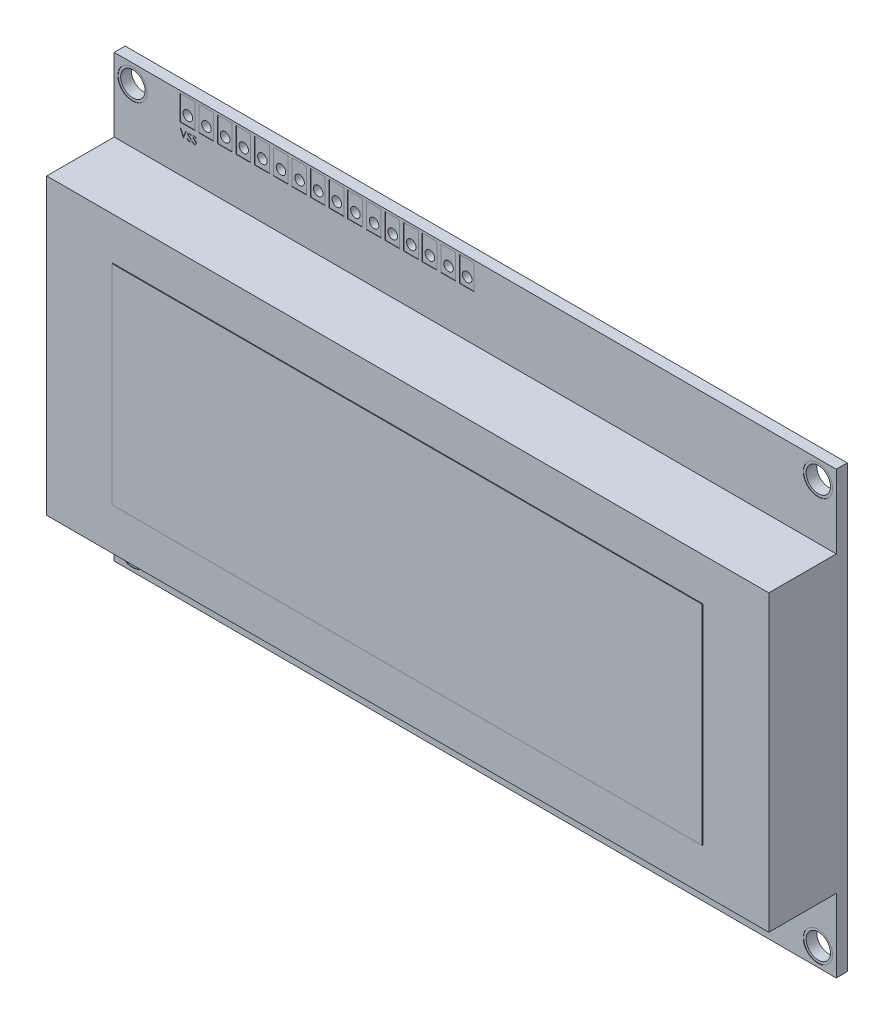
SolidWorks part; units mm, degrees
ref_plane "Front Plane" through (0, 0, 0) normal (0, 0, 1) x (1, 0, 0)
ref_plane "Top Plane" through (0, 0, 0) normal (0, 1, 0) x (1, 0, 0)
ref_plane "Right Plane" through (0, 0, 0) normal (1, 0, 0) x (0, 0, -1)
sketch "Sketch1" plane through (0, 0, 0) normal (0, 0, 1) x (1, 0, 0)
  line L0 (0, 40.8512) -> (0, -48.0365) construction
  line L1 (49.25, -30.05) -> (-49.25, -30.05)
  line L2 (49.25, -30.05) -> (49.25, 30.05)
  line L3 (49.25, 30.05) -> (-49.25, 30.05)
  line L4 (-49.25, -30.05) -> (-49.25, 30.05)
  line L5 (49.25, -30.05) -> (-49.25, 30.05) construction
  line L6 (49.25, 30.05) -> (-49.25, -30.05) construction
  line L7 (-58.2061, 0) -> (68.8537, 0) construction
  circle A0 centre (-46.75, 27.55) radius 1.665
  circle A1 centre (46.75, 27.55) radius 1.665
  circle A2 centre (-46.75, -27.55) radius 1.665
  circle A3 centre (46.75, -27.55) radius 1.665
  circle A4 centre (-39.25, 27.55) radius 0.65
  circle A5 centre (-36.71, 27.55) radius 0.65
  circle A6 centre (-34.17, 27.55) radius 0.65
  circle A7 centre (-31.63, 27.55) radius 0.65
  circle A8 centre (-29.09, 27.55) radius 0.65
  circle A9 centre (-26.55, 27.55) radius 0.65
  circle A10 centre (-24.01, 27.55) radius 0.65
  circle A11 centre (-21.47, 27.55) radius 0.65
  circle A12 centre (-18.93, 27.55) radius 0.65
  circle A13 centre (-16.39, 27.55) radius 0.65
  circle A14 centre (-13.85, 27.55) radius 0.65
  circle A15 centre (-11.31, 27.55) radius 0.65
  circle A16 centre (-8.77, 27.55) radius 0.65
  circle A17 centre (-6.23, 27.55) radius 0.65
  circle A18 centre (-3.69, 27.55) radius 0.65
  circle A19 centre (-1.15, 27.55) radius 0.65
  point P0 (0, 0)
  dimension "D5" = 3.33
  dimension "D6" = 1.3
  dimension "D1" = 98.5
  dimension "D2" = 60.1
  dimension "D3" = 2.5
  dimension "D4" = 2.5
  dimension "D7" = 2.5
  dimension "D8" = 10
  dimension "D10" = 2.54
  dimension "D9" = 16
extrude "Boss-Extrude1" add sketch "Sketch1" along normal mid plane 1.5
sketch "Sketch2" plane through (0, 0, 0.75) normal (0, 0, 1) x (1, 0, 0)
  line L0 (-49.25, 30.05) -> (-49.25, -30.05) construction
  line L1 (49.25, -20.05) -> (-49.25, -20.05)
  line L2 (49.25, -20.05) -> (49.25, 20.05)
  line L3 (49.25, 20.05) -> (-49.25, 20.05)
  line L4 (-49.25, -20.05) -> (-49.25, 20.05)
  line L5 (49.25, -20.05) -> (-49.25, 20.05) construction
  line L6 (49.25, 20.05) -> (-49.25, -20.05) construction
  line L7 (49.25, 30.05) -> (-49.25, 30.05) construction
  point P0 (0, 0)
  dimension "D1" = 10
  dimension "D2" = 40.1
  dimension "D3" = 98.5
extrude "Boss-Extrude2" add sketch "Sketch2" along normal blind 9.2
sketch "Sketch3" plane through (0, 0, 9.95) normal (0, 0, 1) x (1, 0, 0)
  line L0 (-49.25, 20.05) -> (-49.25, -20.05) construction
  line L1 (40.25, -14.25) -> (-40.25, -14.25)
  line L2 (40.25, -14.25) -> (40.25, 14.25)
  line L3 (40.25, 14.25) -> (-40.25, 14.25)
  line L4 (-40.25, -14.25) -> (-40.25, 14.25)
  line L5 (40.25, -14.25) -> (-40.25, 14.25) construction
  line L6 (40.25, 14.25) -> (-40.25, -14.25) construction
  line L7 (49.25, 20.05) -> (-49.25, 20.05) construction
  point P0 (0, 0)
  dimension "D1" = 9
  dimension "D2" = 5.8
extrude "Boss-Extrude3" add sketch "Sketch3" along normal blind 0.1
sketch "Sketch4" plane through (0, 0, 0.75) normal (0, 0, 1) x (1, 0, 0)
  line L0 (0, 45.5389) -> (0, -39.1221) construction
  line L1 (-62.9284, 0) -> (59.0171, 0) construction
  line L2 (-37.71, 29.7169) -> (-37.71, 26.3169)
  line L3 (-40.25, 29.7169) -> (-38.25, 29.7169)
  line L4 (-40.25, 29.7169) -> (-40.25, 26.3169)
  line L5 (-40.25, 26.3169) -> (-38.25, 26.3169)
  line L6 (-38.25, 29.7169) -> (-38.25, 26.3169)
  line L7 (-40.25, 29.7169) -> (-38.25, 26.3169) construction
  line L8 (-40.25, 26.3169) -> (-38.25, 29.7169) construction
  line L9 (-37.71, 29.7169) -> (-35.71, 29.7169)
  line L10 (-35.71, 29.7169) -> (-35.71, 26.3169)
  line L11 (-37.71, 26.3169) -> (-35.71, 26.3169)
  line L12 (-35.17, 29.7169) -> (-35.17, 26.3169)
  line L13 (-35.17, 29.7169) -> (-33.17, 29.7169)
  line L14 (-33.17, 29.7169) -> (-33.17, 26.3169)
  line L15 (-35.17, 26.3169) -> (-33.17, 26.3169)
  line L16 (-32.63, 29.7169) -> (-32.63, 26.3169)
  line L17 (-32.63, 29.7169) -> (-30.63, 29.7169)
  line L18 (-30.63, 29.7169) -> (-30.63, 26.3169)
  line L19 (-32.63, 26.3169) -> (-30.63, 26.3169)
  line L20 (-30.09, 29.7169) -> (-30.09, 26.3169)
  line L21 (-30.09, 29.7169) -> (-28.09, 29.7169)
  line L22 (-28.09, 29.7169) -> (-28.09, 26.3169)
  line L23 (-30.09, 26.3169) -> (-28.09, 26.3169)
  line L24 (-27.55, 29.7169) -> (-27.55, 26.3169)
  line L25 (-27.55, 29.7169) -> (-25.55, 29.7169)
  line L26 (-25.55, 29.7169) -> (-25.55, 26.3169)
  line L27 (-27.55, 26.3169) -> (-25.55, 26.3169)
  line L28 (-25.01, 29.7169) -> (-25.01, 26.3169)
  line L29 (-25.01, 29.7169) -> (-23.01, 29.7169)
  line L30 (-23.01, 29.7169) -> (-23.01, 26.3169)
  line L31 (-25.01, 26.3169) -> (-23.01, 26.3169)
  line L32 (-22.47, 29.7169) -> (-22.47, 26.3169)
  line L33 (-22.47, 29.7169) -> (-20.47, 29.7169)
  line L34 (-20.47, 29.7169) -> (-20.47, 26.3169)
  line L35 (-22.47, 26.3169) -> (-20.47, 26.3169)
  line L36 (-19.93, 29.7169) -> (-19.93, 26.3169)
  line L37 (-19.93, 29.7169) -> (-17.93, 29.7169)
  line L38 (-17.93, 29.7169) -> (-17.93, 26.3169)
  line L39 (-19.93, 26.3169) -> (-17.93, 26.3169)
  line L40 (-17.39, 29.7169) -> (-17.39, 26.3169)
  line L41 (-17.39, 29.7169) -> (-15.39, 29.7169)
  line L42 (-15.39, 29.7169) -> (-15.39, 26.3169)
  line L43 (-17.39, 26.3169) -> (-15.39, 26.3169)
  line L44 (-14.85, 29.7169) -> (-14.85, 26.3169)
  line L45 (-14.85, 29.7169) -> (-12.85, 29.7169)
  line L46 (-12.85, 29.7169) -> (-12.85, 26.3169)
  line L47 (-14.85, 26.3169) -> (-12.85, 26.3169)
  line L48 (-12.31, 29.7169) -> (-12.31, 26.3169)
  line L49 (-12.31, 29.7169) -> (-10.31, 29.7169)
  line L50 (-10.31, 29.7169) -> (-10.31, 26.3169)
  line L51 (-12.31, 26.3169) -> (-10.31, 26.3169)
  line L52 (-9.77, 29.7169) -> (-9.77, 26.3169)
  line L53 (-9.77, 29.7169) -> (-7.77, 29.7169)
  line L54 (-7.77, 29.7169) -> (-7.77, 26.3169)
  line L55 (-9.77, 26.3169) -> (-7.77, 26.3169)
  line L56 (-7.23, 29.7169) -> (-7.23, 26.3169)
  line L57 (-7.23, 29.7169) -> (-5.23, 29.7169)
  line L58 (-5.23, 29.7169) -> (-5.23, 26.3169)
  line L59 (-7.23, 26.3169) -> (-5.23, 26.3169)
  line L60 (-4.69, 29.7169) -> (-4.69, 26.3169)
  line L61 (-4.69, 29.7169) -> (-2.69, 29.7169)
  line L62 (-2.69, 29.7169) -> (-2.69, 26.3169)
  line L63 (-4.69, 26.3169) -> (-2.69, 26.3169)
  line L64 (-2.15, 29.7169) -> (-2.15, 26.3169)
  line L65 (-2.15, 29.7169) -> (-0.15, 29.7169)
  line L66 (-0.15, 29.7169) -> (-0.15, 26.3169)
  line L67 (-2.15, 26.3169) -> (-0.15, 26.3169)
  circle A0 centre (-46.75, 27.55) radius 2.0028
  circle A1 centre (46.75, 27.55) radius 2.0028
  circle A2 centre (46.75, -27.55) radius 2.0028
  circle A3 centre (-46.75, -27.55) radius 2.0028
  point P14 (-39.25, 28.0169)
  dimension "D1" = 2
  dimension "D2" = 3.4
  dimension "D3" = 16
extrude "Cut-Extrude1" cut sketch "Sketch4" against normal blind 0.05
sketch "Sketch5" plane through (0, 0, 0.75) normal (0, 0, 1) x (1, 0, 0)
  line L0 (-40.274, 24.6356) -> (2.9618, 24.6356) construction
  text T0 "VSS" font "Century Gothic" height 1
extrude "Cut-Extrude2" cut sketch "Sketch5" against normal blind 0.05
sketch "Sketch7" plane through (0, 0, 0.7) normal (0, 0, 1) x (1, 0, 0)
  circle A0 centre (-1.15, 27.55) radius 0.65
  circle A1 centre (-3.45, 27.55) radius 0.65
  circle A2 centre (-5.75, 27.55) radius 0.65
  circle A3 centre (-8.05, 27.55) radius 0.65
  circle A4 centre (-10.35, 27.55) radius 0.65
  circle A5 centre (-12.65, 27.55) radius 0.65
  circle A6 centre (-14.95, 27.55) radius 0.65
  circle A7 centre (-17.25, 27.55) radius 0.65
  circle A8 centre (-19.55, 27.55) radius 0.65
  circle A9 centre (-21.85, 27.55) radius 0.65
  circle A10 centre (-24.15, 27.55) radius 0.65
  circle A11 centre (-26.45, 27.55) radius 0.65
  circle A12 centre (-28.75, 27.55) radius 0.65
  circle A13 centre (-31.05, 27.55) radius 0.65
  circle A14 centre (-33.35, 27.55) radius 0.65
  circle A15 centre (-35.65, 27.55) radius 0.65
  dimension "D1" = 16
extrude "Boss-Extrude4" [suppressed] add sketch "Sketch7" against normal blind 15 and the other way blind 0.1
